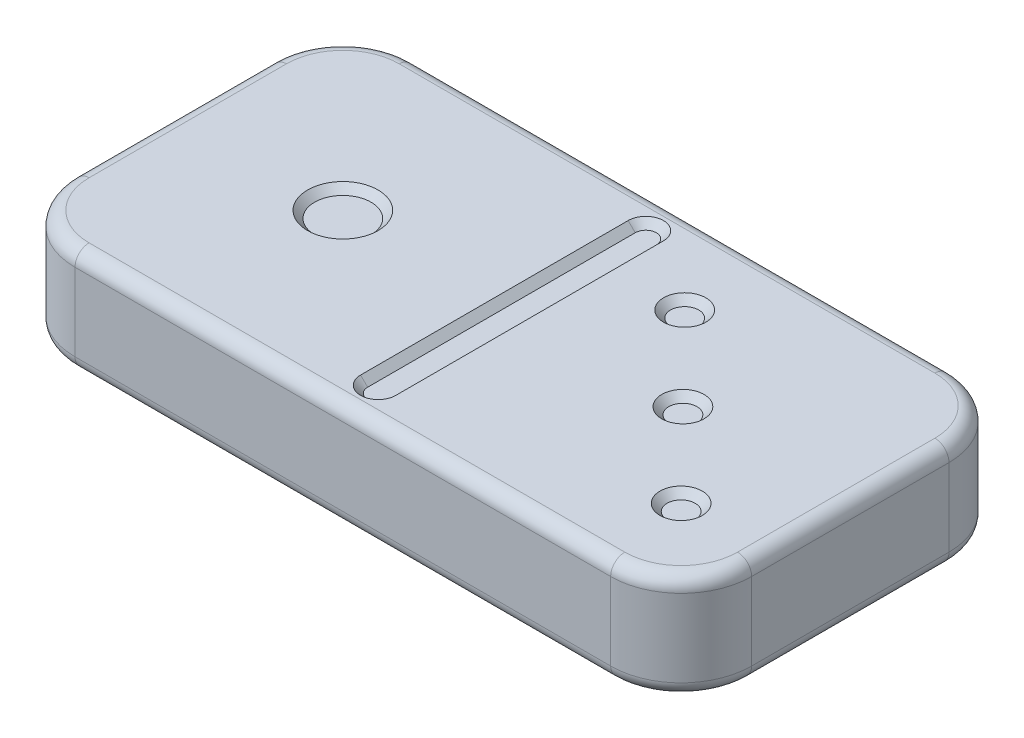
SolidWorks part; units mm, degrees
material "ABS"
ref_plane "Front Plane" through (0, 0, 0) normal (0, 0, 1) x (1, 0, 0)
ref_plane "Top Plane" through (0, 0, 0) normal (0, 1, 0) x (1, 0, 0)
ref_plane "Right Plane" through (0, 0, 0) normal (1, 0, 0) x (0, 0, -1)
sketch "Esquisse1" plane through (0, 0, 0) normal (0, 1, 0) x (1, 0, 0)
  line L1 (0, 0) -> (48, 0)
  line L2 (0, 0) -> (0, 24)
  line L3 (0, 24) -> (48, 24)
  line L4 (48, 0) -> (48, 24)
  dimension "D1" = 48
  dimension "D2" = 24
extrude "Extrusion1" add sketch "Esquisse1" along normal blind 7.5
fillet "Congé2" radius 5 4 edges at (48, 3.75, 0) (48, 3.75, -24) (0, 3.75, 0) (0, 3.75, -24)
fillet "Congé5" radius 1 8 edges at (46.5355, 7.5, -22.5355) (48, 7.5, -12) (46.5355, 7.5, -1.4645) (24, 7.5, 0) (1.4645, 7.5, -1.4645) (0, 7.5, -12) (1.4645, 7.5, -22.5355) (24, 7.5, -24)
fillet "Congé6" radius 1 8 edges at (46.5355, 0, -22.5355) (48, 0, -12) (46.5355, 0, -1.4645) (24, 0, 0) (1.4645, 0, -1.4645) (0, 0, -12) (1.4645, 0, -22.5355) (24, 0, -24)
sketch "Esquisse4" plane through (0, 7.5, 0) normal (0, 1, 0) x (1, 0, 0)
  line L0 (1, 12) -> (47, 12) construction
  line L1 (1, 19) -> (1, 5) construction
  line L2 (47, 5) -> (47, 19) construction
  line L3 (24, 23) -> (24, 1) construction
  line L4 (43, 23) -> (5, 23) construction
  line L5 (5, 1) -> (43, 1) construction
  line L7 (23.75, 21.4914) -> (24.25, 21.4914)
  line L8 (23.75, 21.4914) -> (23.75, 2.5086)
  line L9 (23.75, 2.5086) -> (24.25, 2.5086)
  line L10 (24.25, 21.4914) -> (24.25, 2.5086)
  line L11 (23.75, 21.4914) -> (24.25, 2.5086) construction
  line L12 (23.75, 2.5086) -> (24.25, 21.4914) construction
  point P12 (24, 12)
  dimension "D1" = 0.5
extrude "Extrusion2" cut sketch "Esquisse4" against normal blind 0.5
sketch "Esquisse5" plane through (0, 7.5, 0) normal (0, 1, 0) x (1, 0, 0)
  line L0 (24.25, 21.4914) -> (23.75, 21.4914) construction
  line L1 (23.75, 2.5086) -> (24.25, 2.5086) construction
  circle A0 centre (24, 21.4914) radius 0.25
  circle A1 centre (24, 2.5086) radius 0.25
  dimension "D1" = 0.5
  dimension "D2" = 0.5
extrude "Extrusion3" cut sketch "Esquisse5" against normal blind 0.5
chamfer "Chanfrein1" distance 1 angle 45 4 edges at (24, 7.5, -21.7414) (24.25, 7.5, -12) (24, 7.5, -2.2586) (23.75, 7.5, -12)
sketch "Esquisse9" plane through (0, 7.5, 0) normal (0, 1, 0) x (1, 0, 0)
  line L0 (43, 23) -> (5, 23) construction
  line L1 (25.25, 21.4914) -> (25.25, 2.5086) construction
  line L2 (47, 5) -> (47, 19) construction
  line L3 (5, 1) -> (43, 1) construction
  line L4 (30.25, 18) -> (42, 6) construction
  circle A0 centre (30.25, 18) radius 1.5
  circle A1 centre (36.125, 12) radius 1.5
  circle A2 centre (42, 6) radius 1.5
  dimension "D1" = 3
  dimension "D2" = 3
  dimension "D3" = 3
  dimension "D4" = 5
  dimension "D5" = 5
  dimension "D6" = 5
  dimension "D7" = 5
extrude "Extrusion6" cut sketch "Esquisse9" against normal blind 0.5 draft 45
sketch "Esquisse10" plane through (0, 7.5, 0) normal (0, 1, 0) x (1, 0, 0)
  line L0 (43, 23) -> (5, 23) construction
  line L1 (1, 19) -> (1, 5) construction
  circle A0 centre (12, 12) radius 2.5
  dimension "D1" = 5
  dimension "D2" = 11
  dimension "D3" = 11
extrude "Extrusion8" cut sketch "Esquisse10" against normal blind 0.5 draft 45
